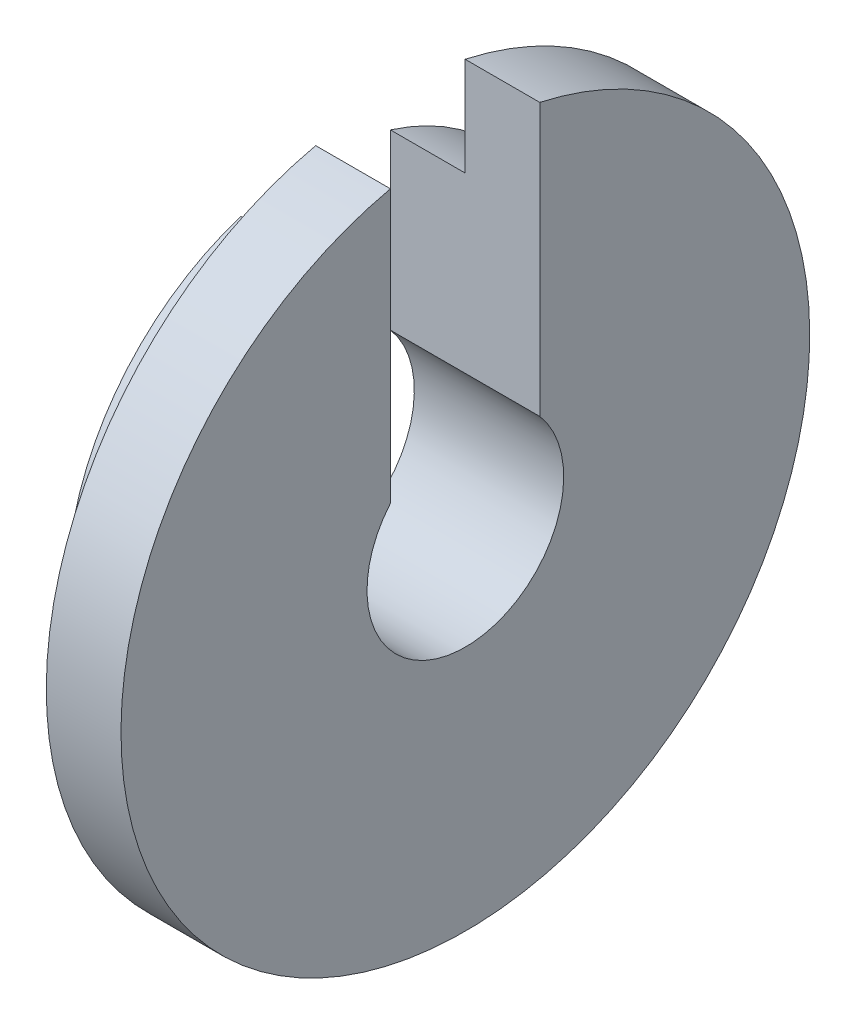
SolidWorks part; units mm, degrees
ref_plane "Front Plane" through (0, 0, 0) normal (0, 0, 1) x (1, 0, 0)
ref_plane "Top Plane" through (0, 0, 0) normal (0, 1, 0) x (1, 0, 0)
ref_plane "Right Plane" through (0, 0, 0) normal (1, 0, 0) x (0, 0, -1)
sketch "Sketch1" plane through (0, 0, 0) normal (1, 0, 0) x (0, 0, -1)
  line L2 (0.7593, 3.4301) -> (0.7593, 0.6558)
  line L4 (-0.7647, 3.4289) -> (-0.7647, 0.6495)
  arc A0 (-0.7647, 0.6495) -> (0.7593, 0.6558) centre (0, 0) ccw
  arc A1 (-0.7647, 3.4289) -> (0.7593, 3.4301) centre (0, 0) ccw
  point P4 (-0.0027, 2.8539)
  dimension "D1" = 1.524
  dimension "D2" = 1.0033
  dimension "D3" = 0.762
extrude "Boss-Extrude1" add sketch "Sketch1" along normal blind 0.762
sketch "Sketch3" plane through (0.762, 0, 0) normal (1, 0, 0) x (0, 0, -1)
  line L0 (-0.7647, 2.4233) -> (-0.7647, 0.6495)
  line L1 (-0.7647, 0.6495) -> (-0.7647, 3.4289) construction
  line L2 (0.7593, 2.425) -> (0.7593, 0.6558)
  line L3 (0.7593, 3.4301) -> (0.7593, 0.6558) construction
  arc A0 (-0.7647, 2.4233) -> (0.7593, 2.425) centre (0, 0) ccw
  arc A1 (-0.7647, 0.6495) -> (0.7593, 0.6558) centre (0, 0) ccw
extrude "Boss-Extrude2" add sketch "Sketch3" against normal blind 1.524
